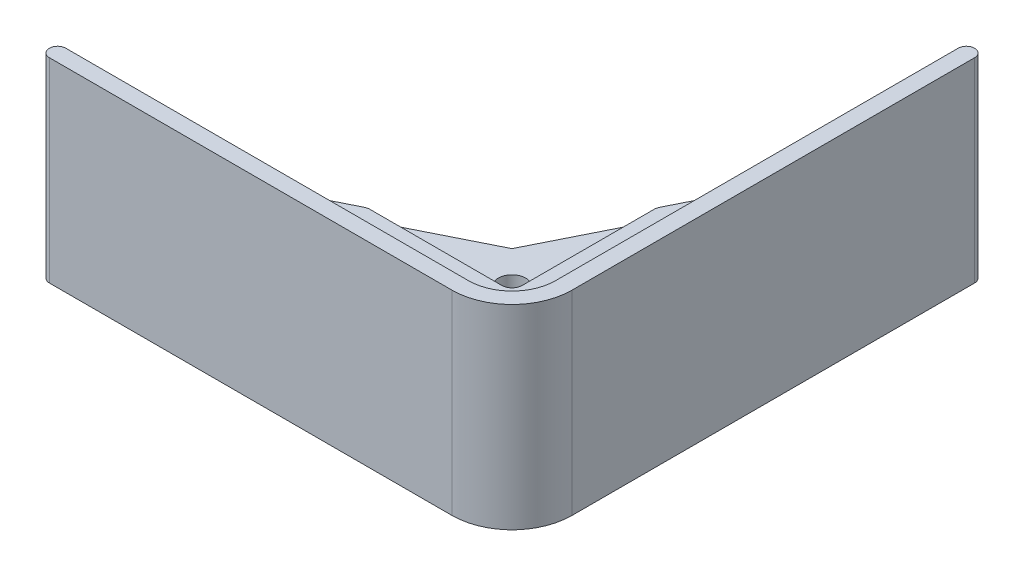
SolidWorks part; units mm, degrees
material "Nylon 101"
ref_plane "Front Plane" through (0, 0, 0) normal (0, 0, 1) x (1, 0, 0)
ref_plane "Top Plane" through (0, 0, 0) normal (0, 1, 0) x (1, 0, 0)
ref_plane "Right Plane" through (0, 0, 0) normal (1, 0, 0) x (0, 0, -1)
sketch "Sketch1" plane through (0, 0, 0) normal (0, 1, 0) x (1, 0, 0)
  line L0 (0, -18.542) -> (-127, -18.542)
  line L1 (18.542, 0) -> (18.542, 127)
  line L2 (-127, -18.542) -> (-127, -13.462)
  line L3 (-127, -13.462) -> (0, -13.462)
  line L4 (13.462, 0) -> (13.462, 127)
  line L5 (13.462, 127) -> (18.542, 127)
  line L6 (-6.0067, 12.0476) -> (-57.1711, -13.462)
  line L7 (-12.0476, 6.0067) -> (13.462, 57.1711)
  circle A0 centre (0, 0) radius 4.2862
  arc A1 (0, -18.542) -> (18.542, 0) centre (0, 0) ccw
  circle A2 centre (0, 0) radius 13.462
  dimension "D1" = 8.5725
  dimension "D4" = 5.08
  dimension "D5" = 127
  dimension "D6" = 26.5
  dimension "D3" = 13.462
extrude "Boss-Extrude1" add sketch "Sketch1" along normal blind 50.8 contours A2 L3 L2 L0 A1 L1 L5 L4 | A2 A0 | A2 L3 | A2 L4 L7 | A2 L6 L7 region at (-63.5, 0, 16.4837) region at (-26.4429, 0, 6.2746) region at (-11.1237, 0, 6.8835) region at (6.2746, 0, -26.4429) region at (-9.6262, 0, -9.6262)
fillet "Fillet2" radius 2.54 4 edges at (13.462, 25.4, -127) (18.542, 25.4, -127) (-127, 25.4, 13.462) (-127, 25.4, 18.542)
ref_plane "Plane1" through (0, 25.4, 0) normal (0, 1, 0) x (1, 0, 0)
sketch "Sketch7" plane through (0, 50.8, 0) normal (0, 1, 0) x (1, 0, 0)
  line L1 (4.826, -4.826) -> (-39.8499, -4.826)
  line L2 (4.826, -4.826) -> (4.826, 39.8499)
  line L3 (4.826, 39.8499) -> (-39.8499, 39.8499)
  line L4 (-39.8499, -4.826) -> (-39.8499, 39.8499)
  line L6 (-10.0378, 10.0378) -> (-57.1711, -13.462) construction
  circle A1 centre (0, 0) radius 4.2862 construction
  dimension "D1" = 4.826
  dimension "D2" = 4.826
extrude "Cut-Extrude3" cut sketch "Sketch7" against normal blind 3.429
fillet "Fillet9" radius 3.175 3 edges at (4.826, 49.0855, -39.8499) (4.826, 49.0855, 4.826) (-39.8499, 49.0855, 4.826)
sketch "Sketch8" plane through (0, 25.4, 0) normal (0, 1, 0) x (1, 0, 0)
  line L0 (0, -13.462) -> (-124.46, -13.462)
  line L10 (13.462, 57.1711) -> (5.1596, 40.519)
  line L11 (4.826, 39.1023) -> (4.826, -1.651)
  line L12 (1.651, -4.826) -> (-39.1023, -4.826)
  line L13 (-40.519, -5.1596) -> (-57.1711, -13.462)
  line L14 (-57.1711, -13.462) -> (-124.46, -13.462)
  line L16 (-124.46, -18.542) -> (0, -18.542)
  line L17 (18.542, 0) -> (18.542, 124.46)
  line L19 (13.462, 124.46) -> (13.462, 57.1711)
  line L26 (-124.46, -18.542) -> (0, -18.542)
  line L27 (18.542, 0) -> (18.542, 124.46)
  line L29 (13.462, 124.46) -> (13.462, 0)
  arc A0 (0, -13.462) -> (13.462, 0) centre (0, 0) ccw
  arc A9 (5.1596, 40.519) -> (4.826, 39.1023) centre (8.001, 39.1023) ccw
  arc A10 (1.651, -4.826) -> (4.826, -1.651) centre (1.651, -1.651) ccw
  arc A11 (-39.1023, -4.826) -> (-40.519, -5.1596) centre (-39.1023, -8.001) ccw
  arc A12 (-124.46, -13.462) -> (-127, -16.002) centre (-124.46, -16.002) ccw
  arc A13 (-127, -16.002) -> (-124.46, -18.542) centre (-124.46, -16.002) ccw
  arc A14 (0, -18.542) -> (18.542, 0) centre (0, 0) ccw
  arc A15 (18.542, 124.46) -> (16.002, 127) centre (16.002, 124.46) ccw
  arc A16 (16.002, 127) -> (13.462, 124.46) centre (16.002, 124.46) ccw
  arc A21 (-124.46, -13.462) -> (-127, -16.002) centre (-124.46, -16.002) ccw
  arc A22 (-127, -16.002) -> (-124.46, -18.542) centre (-124.46, -16.002) ccw
  arc A23 (0, -18.542) -> (18.542, 0) centre (0, 0) ccw
  arc A24 (18.542, 124.46) -> (16.002, 127) centre (16.002, 124.46) ccw
  arc A25 (16.002, 127) -> (13.462, 124.46) centre (16.002, 124.46) ccw
  dimension "D1" = 0
extrude "Boss-Extrude2" add sketch "Sketch8" along normal mid plane 60.325
equation "\"D1@Sketch1\"=.3125+0.025"
